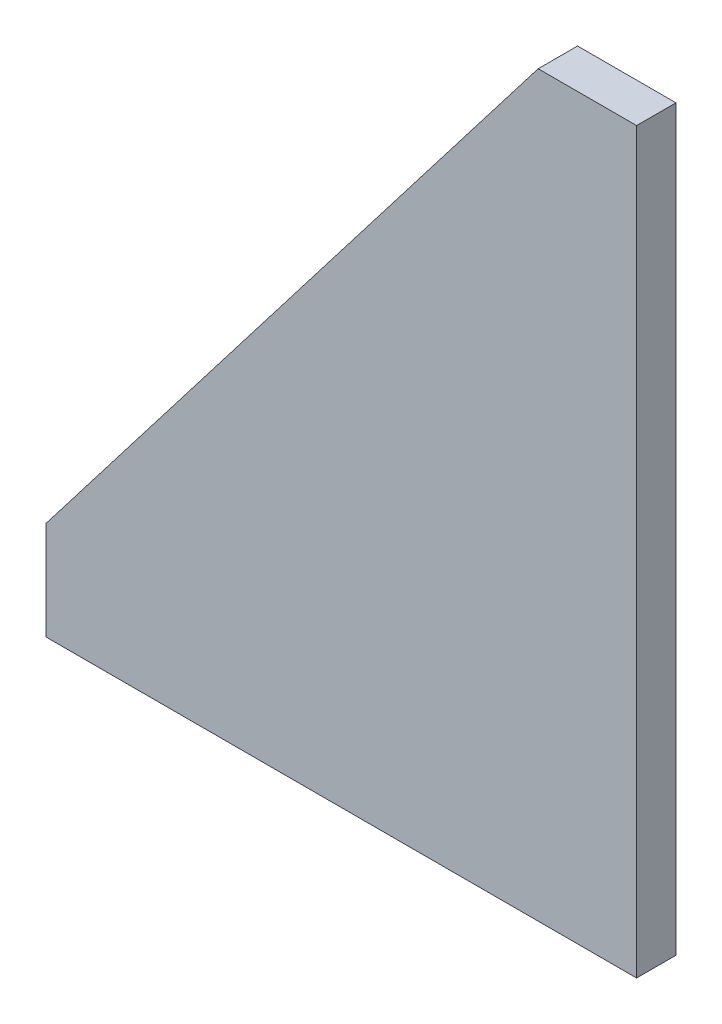
SolidWorks part; units mm, degrees
note: The reader was unsure of these and kept them because the rebuilt part matched: thickness of "Базовая кромка1", "Листовой металл1".
material "Простая углеродистая сталь"
ref_plane "Спереди" through (0, 0, 0) normal (0, 0, 1) x (1, 0, 0)
ref_plane "Сверху" through (0, 0, 0) normal (0, 1, 0) x (1, 0, 0)
ref_plane "Справа" through (0, 0, 0) normal (1, 0, 0) x (0, 0, -1)
sketch "Эскиз1" plane through (0, 0, 0) normal (0, 0, 1) x (1, 0, 0)
  line L0 (0, 0) -> (240, 0) construction
  line L1 (240, 0) -> (240, 20) construction
  line L2 (240, 20) -> (140, 150) construction
  line L3 (140, 150) -> (100, 150) construction
  line L4 (100, 150) -> (0, 20)
  line L5 (0, 20) -> (0, 0)
  line L6 (120, 0) -> (120, 178.6744) construction
  line L7 (0, 0) -> (120, 0)
  line L8 (120, 0) -> (120, 150)
  line L9 (120, 150) -> (100, 150)
  dimension "D1" = 120
  dimension "D2" = 150
  dimension "D3" = 20
  dimension "D4" = 20
base flange "Базовая кромка1" sketch "Эскиз1" thickness 8 reverse thickness direction no parameters "D1"=3
sketch "Сгиб-Линии1" [suppressed] plane through (0, 0, 0) normal (0, 1, 0) x (1, 0, 0)
sketch "Граничная рамка1" [suppressed] plane through (0, 0, 0) normal (0, 1, 0) x (1, 0, 0)
sheet metal parameters "Листовой металл1" thickness 8 parameters "D1"=3, "D7"=10
flat pattern "Развертка1" [suppressed]
sketch "Сгиб-Линии2" plane through (0, 0, 0) normal (0, 1, 0) x (1, 0, 0)
sketch3d "Граничная рамка2" [suppressed]
  line L0 (120, 150, 0) -> (120, 0, 0) construction
  line L1 (0, 150, 0) -> (0, 0, 0) construction
  line L2 (120, 150, 0) -> (0, 150, 0) construction
  line L3 (120, 0, 0) -> (0, 0, 0) construction
